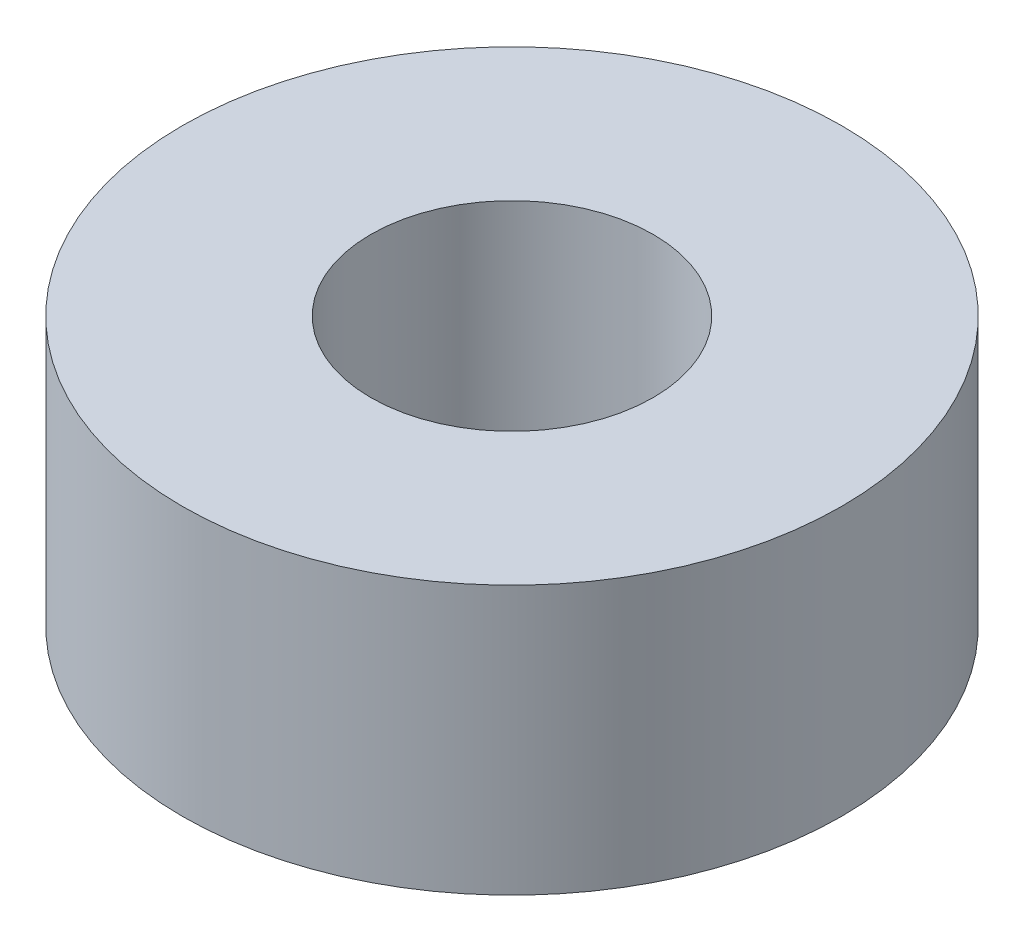
SolidWorks part; units mm, degrees
material "1060 合金"
ref_plane "前视基准面" through (0, 0, 0) normal (0, 0, 1) x (1, 0, 0)
ref_plane "上视基准面" through (0, 0, 0) normal (0, 1, 0) x (1, 0, 0)
ref_plane "右视基准面" through (0, 0, 0) normal (1, 0, 0) x (0, 0, -1)
sketch "草图1" plane through (0, 0, 0) normal (0, 1, 0) x (1, 0, 0)
  circle A0 centre (0, 0) radius 7
  circle A1 centre (0, 0) radius 3
  dimension "D1" = 6
  dimension "D2" = 14
extrude "凸台-拉伸1" add sketch "草图1" along normal blind 5.7
move or copy body "实体-移动/复制1" [suppressed] bodies to move or copy 101
